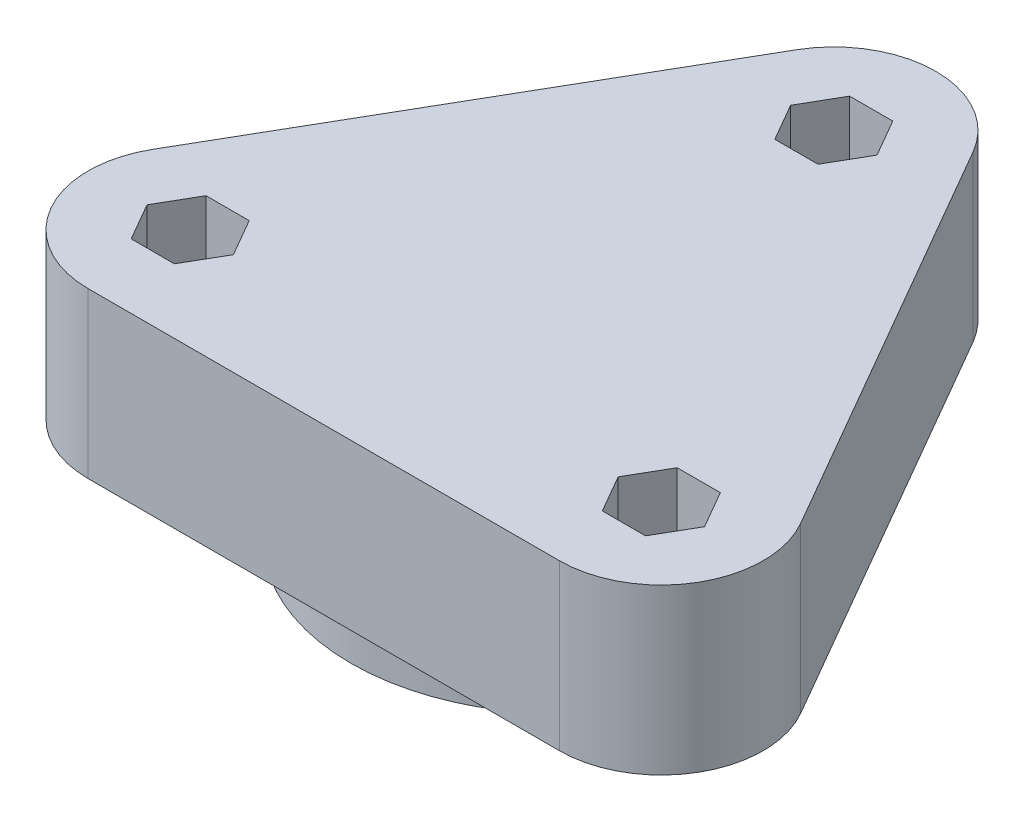
SolidWorks part; units mm, degrees
material "ABS"
ref_plane "Plan de face" through (0, 0, 0) normal (0, 0, 1) x (1, 0, 0)
ref_plane "Plan de dessus" through (0, 0, 0) normal (0, 1, 0) x (1, 0, 0)
ref_plane "Plan de droite" through (0, 0, 0) normal (1, 0, 0) x (0, 0, -1)
sketch "Esquisse1" plane through (0, 0, 0) normal (0, 1, 0) x (1, 0, 0)
  line L0 (-6.4952, 23.75) -> (-23.8157, -6.25)
  line L1 (-17.3205, -17.5) -> (17.3205, -17.5)
  line L2 (6.4952, 23.75) -> (23.8157, -6.25)
  line L3 (0, 20) -> (0, 0) construction
  line L4 (0, 0) -> (-17.3205, -10) construction
  line L6 (17.3205, -10) -> (0, 0) construction
  circle A0 centre (0, 0) radius 11.9
  circle A1 centre (-17.3205, -10) radius 2
  arc A2 (-23.8157, -6.25) -> (-17.3205, -17.5) centre (-17.3205, -10) ccw
  circle A3 centre (0, 20) radius 2
  circle A4 centre (17.3205, -10) radius 2
  circle A5 centre (0, 0) radius 16 construction
  arc A6 (17.3205, -17.5) -> (23.8157, -6.25) centre (17.3205, -10) ccw
  arc A7 (6.4952, 23.75) -> (-6.4952, 23.75) centre (0, 20) ccw
  circle A8 centre (0, 20) radius 4 construction
  dimension "D1" = 23.8
  dimension "D2" = 4
  dimension "D3" = 32
  dimension "D4" = 120
  dimension "D6" = 49.641
  dimension "D8" = 7.5
  dimension "D9" = 20
  dimension "D10" = 8
  dimension "D5" = 17.5
  dimension "D7" = 45
extrude "Boss.-Extru.1" add sketch "Esquisse1" along normal blind 12
sketch "Esquisse2" plane through (0, 12, 0) normal (0, 1, 0) x (1, 0, 0)
  line L0 (23.8157, -6.25) -> (6.4952, 23.75) construction
  line L1 (-18.9082, -7.25) -> (-20.4959, -10)
  line L2 (-20.4959, -10) -> (-18.9082, -12.75)
  line L3 (-18.9082, -12.75) -> (-15.7328, -12.75)
  line L4 (-15.7328, -12.75) -> (-14.1451, -10)
  line L5 (-14.1451, -10) -> (-15.7328, -7.25)
  line L6 (-15.7328, -7.25) -> (-18.9082, -7.25)
  line L7 (-1.5877, 22.75) -> (-3.1754, 20)
  line L8 (-3.1754, 20) -> (-1.5877, 17.25)
  line L9 (-1.5877, 17.25) -> (1.5877, 17.25)
  line L10 (1.5877, 17.25) -> (3.1754, 20)
  line L11 (3.1754, 20) -> (1.5877, 22.75)
  line L12 (1.5877, 22.75) -> (-1.5877, 22.75)
  line L13 (18.9082, -7.25) -> (15.7328, -7.25)
  line L14 (15.7328, -7.25) -> (14.1451, -10)
  line L15 (14.1451, -10) -> (15.7328, -12.75)
  line L16 (15.7328, -12.75) -> (18.9082, -12.75)
  line L17 (18.9082, -12.75) -> (20.4959, -10)
  line L18 (20.4959, -10) -> (18.9082, -7.25)
  line L19 (-6.4952, 23.75) -> (-23.8157, -6.25) construction
  circle A0 centre (-17.3205, -10) radius 2.75 construction
  circle A1 centre (0, 20) radius 2.75 construction
  circle A2 centre (17.3205, -10) radius 2.75 construction
  dimension "D1" = 5.5
extrude "Enlèv. mat.-Extru.1" cut sketch "Esquisse2" against normal blind 5
sketch "Sketch1" plane through (0, 12, 0) normal (0, 1, 0) x (1, 0, 0)
  circle A0 centre (0, 0) radius 11.9 construction
  circle A1 centre (0, 0) radius 11.9
extrude "Boss-Extrude1" add sketch "Sketch1" against normal blind 4 separate body
sketch "Sketch2" plane through (0, 0, 0) normal (0, -1, 0) x (1, 0, 0)
  circle A0 centre (0, 0) radius 11.9
  circle A1 centre (0, 0) radius 15.5
extrude "Boss-Extrude2" add sketch "Sketch2" along normal blind 4.1
sketch "Sketch3" plane through (0, 12, 0) normal (0, 1, 0) x (1, 0, 0)
  line L0 (-1.5877, 22.75) -> (-3.1754, 20) construction
  line L1 (-3.1754, 20) -> (-1.5877, 17.25) construction
  line L2 (-1.5877, 17.25) -> (1.5877, 17.25) construction
  line L3 (-6.4952, 23.75) -> (-23.8157, -6.25)
  line L4 (-17.3205, -17.5) -> (17.3205, -17.5)
  line L5 (23.8157, -6.25) -> (6.4952, 23.75)
  line L6 (-6.4952, 23.75) -> (-23.8157, -6.25)
  line L7 (-17.3205, -17.5) -> (17.3205, -17.5)
  line L8 (23.8157, -6.25) -> (6.4952, 23.75)
  line L9 (1.5877, 17.25) -> (3.1754, 20) construction
  line L10 (3.1754, 20) -> (1.5877, 22.75) construction
  line L11 (1.5877, 22.75) -> (-1.5877, 22.75) construction
  line L12 (18.9082, -12.75) -> (20.4959, -10) construction
  line L13 (14.1451, -10) -> (15.7328, -12.75) construction
  line L14 (15.7328, -12.75) -> (18.9082, -12.75) construction
  line L15 (20.4959, -10) -> (18.9082, -7.25) construction
  line L16 (18.9082, -7.25) -> (15.7328, -7.25) construction
  line L17 (15.7328, -7.25) -> (14.1451, -10) construction
  line L18 (-18.9082, -7.25) -> (-20.4959, -10) construction
  line L19 (-20.4959, -10) -> (-18.9082, -12.75) construction
  line L20 (-18.9082, -12.75) -> (-15.7328, -12.75) construction
  line L21 (-15.7328, -12.75) -> (-14.1451, -10) construction
  line L22 (-14.1451, -10) -> (-15.7328, -7.25) construction
  line L23 (-15.7328, -7.25) -> (-18.9082, -7.25) construction
  line L24 (-1.5877, 22.75) -> (-3.1754, 20)
  line L25 (-3.1754, 20) -> (-1.5877, 17.25)
  line L26 (-1.5877, 17.25) -> (1.5877, 17.25)
  line L27 (1.5877, 17.25) -> (3.1754, 20)
  line L28 (3.1754, 20) -> (1.5877, 22.75)
  line L29 (1.5877, 22.75) -> (-1.5877, 22.75)
  line L30 (18.9082, -12.75) -> (20.4959, -10)
  line L31 (14.1451, -10) -> (15.7328, -12.75)
  line L32 (15.7328, -12.75) -> (18.9082, -12.75)
  line L33 (20.4959, -10) -> (18.9082, -7.25)
  line L34 (18.9082, -7.25) -> (15.7328, -7.25)
  line L35 (15.7328, -7.25) -> (14.1451, -10)
  line L36 (-18.9082, -7.25) -> (-20.4959, -10)
  line L37 (-20.4959, -10) -> (-18.9082, -12.75)
  line L38 (-18.9082, -12.75) -> (-15.7328, -12.75)
  line L39 (-15.7328, -12.75) -> (-14.1451, -10)
  line L40 (-14.1451, -10) -> (-15.7328, -7.25)
  line L41 (-15.7328, -7.25) -> (-18.9082, -7.25)
  arc A3 (6.4952, 23.75) -> (-6.4952, 23.75) centre (0, 20) ccw
  arc A4 (-23.8157, -6.25) -> (-17.3205, -17.5) centre (-17.3205, -10) ccw
  arc A5 (17.3205, -17.5) -> (23.8157, -6.25) centre (17.3205, -10) ccw
  arc A6 (6.4952, 23.75) -> (-6.4952, 23.75) centre (0, 20) ccw
  arc A7 (-23.8157, -6.25) -> (-17.3205, -17.5) centre (-17.3205, -10) ccw
  arc A8 (17.3205, -17.5) -> (23.8157, -6.25) centre (17.3205, -10) ccw
  dimension "D1" = 0
extrude "Boss-Extrude3" add sketch "Sketch3" along normal blind 0.1
